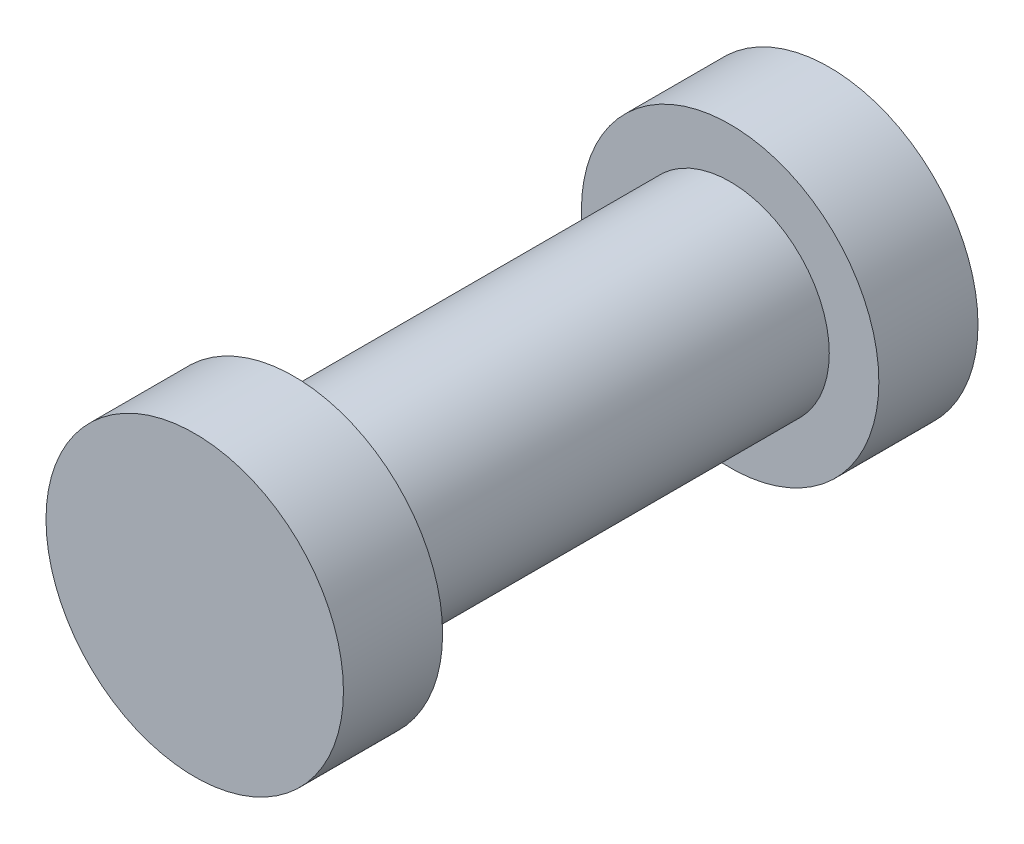
SolidWorks part; units mm, degrees
ref_plane "Front Plane" through (0, 0, 0) normal (0, 0, 1) x (1, 0, 0)
ref_plane "Top Plane" through (0, 0, 0) normal (0, 1, 0) x (1, 0, 0)
ref_plane "Right Plane" through (0, 0, 0) normal (1, 0, 0) x (0, 0, -1)
sketch "Sketch1" plane through (0, 0, 0) normal (0, 0, 1) x (1, 0, 0)
  circle A0 centre (0, 0) radius 5
  circle A1 centre (0, 0) radius 7.5
  dimension "D1" = 10
  dimension "D2" = 15
extrude "Boss-Extrude1" add sketch "Sketch1" along normal blind 32 contours A0
extrude "Boss-Extrude2" add sketch "Sketch1<4>" along normal blind 5
sketch "Sketch1<4>" plane through (0, 0, 0) normal (0, 0, 1) x (1, 0, 0) same geometry as "Sketch1"
extrude "Boss-Extrude3" add sketch "Sketch1<5>" along normal blind 5 from offset 27
sketch "Sketch1<5>" plane through (0, 0, 0) normal (0, 0, 1) x (1, 0, 0) same geometry as "Sketch1"
